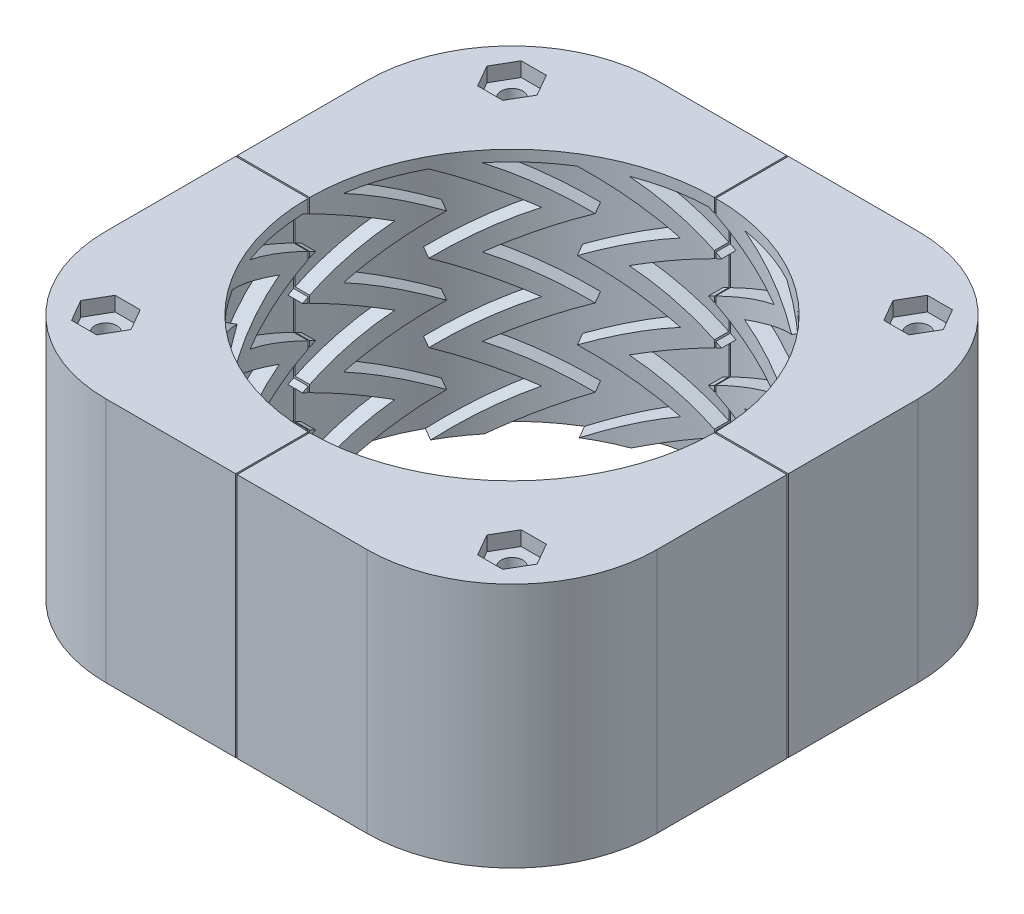
SolidWorks part; units mm, degrees
material "ABS"
ref_plane "Спереди" through (0, 0, 0) normal (0, 0, 1) x (1, 0, 0)
ref_plane "Сверху" through (0, 0, 0) normal (0, 1, 0) x (1, 0, 0)
ref_plane "Справа" through (0, 0, 0) normal (1, 0, 0) x (0, 0, -1)
sketch "Эскиз2" plane through (0, 0, 0) normal (0, 1, 0) x (1, 0, 0)
  line L1 (38, -38) -> (-38, -38)
  line L2 (38, -38) -> (38, 38)
  line L3 (38, 38) -> (-38, 38)
  line L4 (-38, -38) -> (-38, 38)
  line L5 (38, -38) -> (-38, 38) construction
  line L6 (38, 38) -> (-38, -38) construction
  point P0 (0, 0)
  dimension "D1" = 76
  dimension "D2" = 76
extrude "Бобышка-Вытянуть1" add sketch "Эскиз2" along normal blind 42
sketch "Эскиз3" plane through (0, 0, 0) normal (1, 0, 0) x (0, 0, -1)
  line L0 (0, 41.3522) -> (0, -3.1956) construction
  line L1 (-34.4708, 21) -> (34.6551, 21) construction
  line L3 (-28, 42) -> (-28, 8)
  line L4 (-23, 6) -> (0, 6)
  line L5 (0, 6) -> (0, 42)
  line L7 (-38, 42) -> (38, 42) construction
  line L8 (-38, 0) -> (38, 0) construction
  line L9 (-28, 42) -> (0, 42)
  line L10 (-28, 8) -> (-23, 8)
  line L11 (-23, 8) -> (-23, 6)
  line L12 (-23, 8) -> (-21, 6)
  dimension "D1" = 6
  dimension "D2" = 56
  dimension "D3" = 2
  dimension "D4" = 42
  dimension "D5" = 2
revolve "Вырез-Повернуть1" cut sketch "Эскиз3" angle 360 about L5 region at (0, 24.2055, 13.8678)
sketch "Эскиз4" plane through (0, 6, 0) normal (0, 1, 0) x (1, 0, 0)
  circle A0 centre (0, 0) radius 1.5
  dimension "D1" = 3
extrude "Вырез-Вытянуть1" cut sketch "Эскиз4" against normal up to next
fillet "Скругление1" radius 20 4 edges at (-38, 21, 38) (-38, 21, -38) (38, 21, -38) (38, 21, 38)
ref_plane "Плоскость5" through (23, 0, 0) normal (1, 0, 0) x (0, 0, -1)
sketch "Эскиз7" plane through (23, 0, 0) normal (1, 0, 0) x (0, 0, -1)
  line L0 (0, 44.0212) -> (0, -3.9515) construction
  line L1 (-41.4881, 8) -> (37.3044, 8) construction
  line L3 (-41.4881, 40.5) -> (37.3044, 40.5) construction
  line L4 (0.8993, 40.5) -> (10, 40.5)
  line L5 (0.8993, 40.5) -> (-10, 35.1667)
  line L6 (10, 40.5) -> (-0.8993, 35.1667)
  line L7 (-10, 35.1667) -> (-0.8993, 35.1667)
  line L8 (-10, 35.1667) -> (-0.8993, 35.1667)
  line L9 (-10, 35.1667) -> (0.8993, 29.8333)
  line L10 (-0.8993, 35.1667) -> (10, 29.8333)
  line L11 (0.8993, 29.8333) -> (10, 29.8333)
  line L12 (0.8993, 29.8333) -> (10, 29.8333)
  line L13 (0.8993, 29.8333) -> (-10, 24.5)
  line L14 (10, 29.8333) -> (-0.8993, 24.5)
  line L15 (-10, 24.5) -> (-0.8993, 24.5)
  line L16 (-0.8993, 24.5) -> (-10, 24.5)
  line L17 (-0.8993, 24.5) -> (10, 19.1667)
  line L18 (-10, 24.5) -> (0.8993, 19.1667)
  line L19 (10, 19.1667) -> (0.8993, 19.1667)
  line L20 (0.8993, 19.1667) -> (10, 19.1667)
  line L21 (0.8993, 19.1667) -> (-10, 13.8333)
  line L22 (10, 19.1667) -> (-0.8993, 13.8333)
  line L23 (-10, 13.8333) -> (-0.8993, 13.8333)
  line L24 (-0.8993, 13.8333) -> (-10, 13.8333)
  line L25 (-0.8993, 13.8333) -> (10, 8)
  line L26 (-10, 13.8333) -> (0.8993, 8)
  line L27 (10, 8) -> (0.8993, 8)
  line L28 (-10, 41.9456) -> (-10, -2.9296)
  line L29 (10, 41.9456) -> (10, -2.9296)
  line L30 (-38, 0) -> (-18, 0) construction
  dimension "D1" = 32.5
  dimension "D2" = 5.3333
  dimension "D3" = 5.3333
  dimension "D4" = 5.3333
  dimension "D5" = 5.3333
  dimension "D6" = 5.3333
  dimension "D7" = 4
  dimension "D8" = 20
  dimension "D9" = 8
extrude "Вырез-Вытянуть3" cut sketch "Эскиз7" along normal blind 8 contours L5 L7 L6 L4 | L9 L11 L10 L7 | L13 L15 L14 L11 | L19 L17 L15 L18 | L21 L23 L22 L19 | L27 L25 L23 L26 region at (23, 37.8333, 0) region at (23, 32.5, 0) region at (23, 27.1667, 0) region at (23, 21.8333, 0) region at (23, 16.5, 0) region at (23, 10.9167, 0)
pattern_circular "Круговой массив1" count 12 over 360 about axis through (0, 8, 0) along (0, -1, 0) of "Вырез-Вытянуть3"
sketch "Эскиз8" plane through (0, 0, 0) normal (1, 0, 0) x (0, 0, -1)
  line L0 (0, 47.5076) -> (0, -4.6512) construction
  line L2 (0, 40.5) -> (-30, 40.5)
  line L3 (0, 40.5) -> (0, 8)
  line L4 (0, 8) -> (-30, 8)
  line L5 (-30, 40.5) -> (-30, 8)
  line L6 (0.8993, 40.5) -> (10, 40.5) construction
  line L8 (-30, 40.5) -> (-32, 40.5)
  line L9 (-30, 40.5) -> (-30, 8)
  line L10 (-30, 8) -> (-32, 8)
  line L11 (-32, 40.5) -> (-32, 8)
  line L12 (-38, 0) -> (-18, 0) construction
  dimension "D1" = 60
  dimension "D2" = 2
  dimension "D3" = 8
revolve "Повернуть1" add sketch "Эскиз8" angle 360 about L0 region at (0, 24.25, 31)
ref_plane "Плоскость7" through (0, 7.9, 0) normal (0, 1, 0) x (1, 0, 0)
sketch "Эскиз9" plane through (0, 7.9, 0) normal (0, 1, 0) x (1, 0, 0)
  line L0 (0, 36.4102) -> (0, -36.7712) construction
  line L1 (-38.0796, 0) -> (37.9894, 0) construction
  line L2 (-0.1, 0.1) -> (-0.1, 40.8988)
  line L3 (-0.1, -40.8988) -> (0.1, -40.8988)
  line L4 (-0.1, -40.8988) -> (-0.1, -0.1)
  line L5 (-0.1, 40.8988) -> (0.1, 40.8988)
  line L6 (0.1, -40.8988) -> (0.1, -0.1)
  line L7 (-0.1, -40.8988) -> (0.1, 40.8988) construction
  line L8 (-0.1, 40.8988) -> (0.1, -40.8988) construction
  line L9 (42.7981, -0.1) -> (0.1, -0.1)
  line L10 (42.7981, -0.1) -> (42.7981, 0.1)
  line L11 (42.7981, 0.1) -> (0.1, 0.1)
  line L12 (-42.8883, -0.1) -> (-42.8883, 0.1)
  line L13 (42.7981, -0.1) -> (-42.8883, 0.1) construction
  line L14 (42.7981, 0.1) -> (-42.8883, -0.1) construction
  line L15 (-0.1, 0.1) -> (-42.8883, 0.1)
  line L16 (-0.1, -0.0001) -> (-0.1, 0.0001)
  line L17 (-0.1, -0.1) -> (-42.8883, -0.1)
  line L18 (0.0002, -0.1) -> (-0.0002, -0.1)
  line L19 (0.1, -0.0003) -> (0.1, 0.0003)
  line L20 (0.1, 0.1) -> (0.1, 40.8988)
  line L21 (0.0002, 0.1) -> (-0.0002, 0.1)
  point P5 (0, 0)
  point P10 (-0.0451, 0)
  dimension "D1" = 0.2
  dimension "D2" = 0.2
extrude "Вырез-Вытянуть5" cut sketch "Эскиз9" along normal through all contours L11 L20 L5 L2 L15 L12 L17 L4 L3 L6 L9 L10 region at (-0.0231, 7.9, 0)
sketch "Эскиз10" plane through (0, 0, 0) normal (1, 0, 0) x (0, 0, -1)
  line L0 (0, 46.355) -> (0, -3.6398) construction
  line L1 (-45.8168, 7.9) -> (-45.8168, -6.2233)
  line L2 (-38, 7.9) -> (-38, 42) construction
  line L7 (-0.1, 8) -> (-22.9998, 8) construction
  line L13 (48.9241, 8) -> (-38, 8) construction
  line L48 (-36, 8) -> (-36, 10) construction
  line L49 (-45.8168, -6.2233) -> (0, -6.2233)
  line L50 (-36, 10) -> (-32, 10) construction
  line L51 (-32, 10) -> (-32, 8) construction
  line L52 (-27.9998, 8) -> (-27.9998, 8.5348) construction
  line L54 (-35.9, 7.9) -> (-35.9, 8.0302)
  line L57 (-35.9, 7.9) -> (-38, 8.3306) construction
  line L58 (-35.9, 8.0302) -> (-38, 7.9) construction
  line L59 (-35.9, 9.9) -> (-36.1, 9.9)
  line L60 (-35.9, 9.9) -> (-35.9, 8.1)
  line L61 (-35.9, 8.1) -> (-36.1, 8.1)
  line L62 (-36.1, 9.9) -> (-36.1, 8.1)
  line L63 (-35.9, 9.9) -> (-36.1, 8.1) construction
  line L64 (-35.9, 8.1) -> (-36.1, 9.9) construction
  line L65 (-31.9, 9.9) -> (-36.1, 9.9)
  line L66 (-31.9, 9.9) -> (-31.9, 10.1)
  line L67 (-31.9, 10.1) -> (-36.1, 10.1)
  line L68 (-36.1, 9.9) -> (-36.1, 10.1)
  line L69 (-31.9, 9.9) -> (-36.1, 10.1) construction
  line L70 (-31.9, 10.1) -> (-36.1, 9.9) construction
  line L71 (-31.9, 8.1) -> (-32.1, 8.1)
  line L72 (-31.9, 8.1) -> (-31.9, 9.9)
  line L73 (-31.9, 9.9) -> (-32.1, 9.9)
  line L74 (-32.1, 8.1) -> (-32.1, 9.9)
  line L75 (-31.9, 8.1) -> (-32.1, 9.9) construction
  line L76 (-31.9, 9.9) -> (-32.1, 8.1) construction
  line L77 (-27.9998, 8.1) -> (-32.1, 8.1)
  line L78 (-27.9998, 8.1) -> (-27.9998, 7.9)
  line L79 (-27.9998, 7.9) -> (-32.1, 7.9)
  line L80 (-32.1, 8.1) -> (-32.1, 7.9)
  line L81 (-27.9998, 8.1) -> (-32.1, 7.9) construction
  line L82 (-27.9998, 7.9) -> (-32.1, 8.1) construction
  line L83 (0, -6.2233) -> (0, 8.1)
  line L84 (-35.9, 7.9) -> (-45.8168, 7.9)
  line L85 (-35.9, 7.9) -> (-35.9, 8.1)
  line L86 (-35.9, 8.1) -> (-45.8168, 8.1)
  line L87 (-45.8168, 7.9) -> (-45.8168, 8.1)
  line L88 (0, 8.1) -> (-31.9, 8.1)
  point P11 (-36.3877, 8)
  point P18 (-36, 9)
  point P23 (-34, 10)
  point P28 (-32, 9)
  point P33 (-30.0499, 8)
  dimension "D1" = 2
  dimension "D2" = 4
  dimension "D3" = 2
  dimension "D5" = 0.2
  dimension "D4" = 0.2
  dimension "D6" = 0.2
revolve "Вырез-Повернуть3" cut sketch "Эскиз10" angle 360 about L0 region at (0, 8, 40.8584) region at (0, 9, 36) region at (0, 10, 34) region at (0, 8, 30.0499) region at (0, 9, 32)
sketch "Эскиз11" plane through (0, 0, 0) normal (0, 1, 0) x (1, 0, 0)
  line L1 (28, -28) -> (-28, -28)
  line L2 (28, -28) -> (28, 28)
  line L3 (28, 28) -> (-28, 28)
  line L4 (-28, -28) -> (-28, 28)
  line L5 (28, -28) -> (-28, 28) construction
  line L6 (28, 28) -> (-28, -28) construction
  circle A0 centre (-28, 28) radius 1.5
  circle A1 centre (28, 28) radius 1.5
  circle A2 centre (28, -28) radius 1.5
  circle A3 centre (-28, -28) radius 1.5
  point P0 (0, 0)
  dimension "D3" = 3
  dimension "D1" = 56
  dimension "D2" = 56
extrude "Вырез-Вытянуть6" cut sketch "Эскиз11" along normal through all contours A0 | A1 | A2 | A3
sketch "Эскиз12" plane through (0, 0, 0) normal (0, 1, 0) x (1, 0, 0)
  line L0 (0, -39.825) -> (0, 40.7068) construction
  line L1 (-42.7151, 0) -> (42.0294, 0) construction
  line L3 (-29.7321, -31) -> (-26.2679, -31)
  line L4 (-26.2679, -31) -> (-24.5359, -28)
  line L5 (-24.5359, -28) -> (-26.2679, -25)
  line L6 (-26.2679, -25) -> (-29.7321, -25)
  line L7 (-29.7321, -25) -> (-31.4641, -28)
  line L8 (-31.4641, -28) -> (-29.7321, -31)
  line L9 (26.2679, -31) -> (29.7321, -31)
  line L10 (29.7321, -31) -> (31.4641, -28)
  line L11 (31.4641, -28) -> (29.7321, -25)
  line L12 (29.7321, -25) -> (26.2679, -25)
  line L13 (26.2679, -25) -> (24.5359, -28)
  line L14 (24.5359, -28) -> (26.2679, -31)
  line L15 (26.2679, 25) -> (29.7321, 25)
  line L16 (29.7321, 25) -> (31.4641, 28)
  line L17 (31.4641, 28) -> (29.7321, 31)
  line L18 (29.7321, 31) -> (26.2679, 31)
  line L19 (26.2679, 31) -> (24.5359, 28)
  line L20 (24.5359, 28) -> (26.2679, 25)
  line L21 (-29.7321, 25) -> (-26.2679, 25)
  line L22 (-26.2679, 25) -> (-24.5359, 28)
  line L23 (-24.5359, 28) -> (-26.2679, 31)
  line L24 (-26.2679, 31) -> (-29.7321, 31)
  line L25 (-29.7321, 31) -> (-31.4641, 28)
  line L26 (-31.4641, 28) -> (-29.7321, 25)
  line L27 (-1.7321, -3) -> (1.7321, -3)
  line L28 (1.7321, -3) -> (3.4641, 0)
  line L29 (3.4641, 0) -> (1.7321, 3)
  line L30 (1.7321, 3) -> (-1.7321, 3)
  line L31 (-1.7321, 3) -> (-3.4641, 0)
  line L32 (-3.4641, 0) -> (-1.7321, -3)
  circle A0 centre (-28, -28) radius 3 construction
  circle A1 centre (28, -28) radius 3 construction
  circle A2 centre (28, 28) radius 3 construction
  circle A3 centre (-28, 28) radius 3 construction
  circle A4 centre (0, 0) radius 3 construction
  dimension "D1" = 6
extrude "Вырез-Вытянуть7" cut sketch "Эскиз12" along normal blind 2
sketch "Эскиз13" plane through (0, 42, 0) normal (0, 1, 0) x (1, 0, 0)
  line L1 (-29.7321, 31) -> (-31.4641, 28)
  line L2 (-31.4641, 28) -> (-29.7321, 25)
  line L3 (-29.7321, 25) -> (-26.2679, 25)
  line L4 (-26.2679, 25) -> (-24.5359, 28)
  line L5 (-24.5359, 28) -> (-26.2679, 31)
  line L6 (-26.2679, 31) -> (-29.7321, 31)
  line L7 (26.2679, 31) -> (24.5359, 28)
  line L8 (24.5359, 28) -> (26.2679, 25)
  line L9 (26.2679, 25) -> (29.7321, 25)
  line L10 (29.7321, 25) -> (31.4641, 28)
  line L11 (31.4641, 28) -> (29.7321, 31)
  line L12 (29.7321, 31) -> (26.2679, 31)
  line L13 (26.2679, -25) -> (24.5359, -28)
  line L14 (24.5359, -28) -> (26.2679, -31)
  line L15 (26.2679, -31) -> (29.7321, -31)
  line L16 (29.7321, -31) -> (31.4641, -28)
  line L17 (31.4641, -28) -> (29.7321, -25)
  line L18 (29.7321, -25) -> (26.2679, -25)
  line L19 (-29.7321, -25) -> (-31.4641, -28)
  line L20 (-31.4641, -28) -> (-29.7321, -31)
  line L21 (-29.7321, -31) -> (-26.2679, -31)
  line L22 (-26.2679, -31) -> (-24.5359, -28)
  line L23 (-24.5359, -28) -> (-26.2679, -25)
  line L24 (-26.2679, -25) -> (-29.7321, -25)
  circle A0 centre (-28, 28) radius 3 construction
  circle A1 centre (28, 28) radius 3 construction
  circle A2 centre (28, -28) radius 3 construction
  circle A3 centre (-28, -28) radius 3 construction
  dimension "D1" = 6
extrude "Вырез-Вытянуть8" cut sketch "Эскиз13" against normal blind 2
ref_plane "Плоскость6" [suppressed] through (0, 42.2, 0) normal (0, 1, 0) x (1, 0, 0)
sketch "Эскиз14" [suppressed] plane through (0, 42.2, 0) normal (0, 1, 0) x (1, 0, 0)
  line L0 (-0.1, 38) -> (-18, 38) construction
  line L1 (18, -38) -> (-18, -38)
  line L2 (38, -18) -> (38, 18)
  line L3 (18, 38) -> (-18, 38)
  line L4 (-38, -18) -> (-38, 18)
  line L5 (38, -38) -> (-38, 38) construction
  line L6 (38, 38) -> (-38, -38) construction
  line L7 (-38, 18) -> (-38, 0.1) construction
  arc A0 (-18, -38) -> (-38, -18) centre (-18, -18) cw
  arc A1 (18, -38) -> (38, -18) centre (18, -18) ccw
  arc A2 (38, 18) -> (18, 38) centre (18, 18) ccw
  arc A3 (-18, 38) -> (-38, 18) centre (-18, 18) ccw
  circle A4 centre (-28, 28) radius 1.5
  circle A5 centre (28, 28) radius 1.5
  circle A6 centre (28, -28) radius 1.5
  circle A7 centre (-28, -28) radius 1.5
  circle A8 centre (0, 0) radius 1.5
  point P0 (0, 0)
  point P34 (0, 0)
  dimension "D1" = 20
extrude "Бобышка-Вытянуть2" [suppressed] add sketch "Эскиз14" along normal blind 6
sketch "Эскиз15" [suppressed] plane through (0, 48.2, 0) normal (0, 1, 0) x (1, 0, 0)
  line L1 (-29.7321, 31) -> (-31.4641, 28)
  line L2 (-31.4641, 28) -> (-29.7321, 25)
  line L3 (-29.7321, 25) -> (-26.2679, 25)
  line L4 (-26.2679, 25) -> (-24.5359, 28)
  line L5 (-24.5359, 28) -> (-26.2679, 31)
  line L6 (-26.2679, 31) -> (-29.7321, 31)
  line L7 (-1.7321, 3) -> (-3.4641, 0)
  line L8 (-3.4641, 0) -> (-1.7321, -3)
  line L9 (-1.7321, -3) -> (1.7321, -3)
  line L10 (1.7321, -3) -> (3.4641, 0)
  line L11 (3.4641, 0) -> (1.7321, 3)
  line L12 (1.7321, 3) -> (-1.7321, 3)
  line L13 (26.2679, 31) -> (24.5359, 28)
  line L14 (24.5359, 28) -> (26.2679, 25)
  line L15 (26.2679, 25) -> (29.7321, 25)
  line L16 (29.7321, 25) -> (31.4641, 28)
  line L17 (31.4641, 28) -> (29.7321, 31)
  line L18 (29.7321, 31) -> (26.2679, 31)
  line L19 (26.2679, -25) -> (24.5359, -28)
  line L20 (24.5359, -28) -> (26.2679, -31)
  line L21 (26.2679, -31) -> (29.7321, -31)
  line L22 (29.7321, -31) -> (31.4641, -28)
  line L23 (31.4641, -28) -> (29.7321, -25)
  line L24 (29.7321, -25) -> (26.2679, -25)
  line L25 (-29.7321, -25) -> (-31.4641, -28)
  line L26 (-31.4641, -28) -> (-29.7321, -31)
  line L27 (-29.7321, -31) -> (-26.2679, -31)
  line L28 (-26.2679, -31) -> (-24.5359, -28)
  line L29 (-24.5359, -28) -> (-26.2679, -25)
  line L30 (-26.2679, -25) -> (-29.7321, -25)
  circle A0 centre (-28, 28) radius 3 construction
  circle A1 centre (0, 0) radius 3 construction
  circle A2 centre (28, 28) radius 3 construction
  circle A3 centre (28, -28) radius 3 construction
  circle A4 centre (-28, -28) radius 3 construction
  dimension "D1" = 6
extrude "Вырез-Вытянуть9" [suppressed] cut sketch "Эскиз15" against normal blind 2
revolve "Вырез-Повернуть21" cut sketch "Эскиз10<6>" angle 359.999 about L0 region at (0, 0.9919, 22.9605) region at (0, 8, 40.8584) region at (0, 9, 36) region at (0, 10, 34) region at (0, 8, 30.0499) region at (0, 9, 32)
sketch "Эскиз10<6>" plane through (0, 0, 0) normal (1, 0, 0) x (0, 0, -1) same geometry as "Эскиз10"
sketch "Эскиз16" plane through (0, 0, 0) normal (1, 0, 0) x (0, 0, -1)
  line L1 (-38, 8.1) -> (38.9666, 8.1)
  line L2 (-38, 8.1) -> (-38, -5.4859)
  line L3 (-38, -5.4859) -> (38.9666, -5.4859)
  line L4 (38.9666, 8.1) -> (38.9666, -5.4859)
extrude "Вырез-Вытянуть10" cut sketch "Эскиз16" against normal through all both and the other way through all
equation "\"D2@Эскиз2\"=\"D1@Эскиз2\""
equation "\"D4@Эскиз7\"= \"D2@Эскиз7\""
equation "\"D5@Эскиз7\"=\"D2@Эскиз7\""
equation "\"D6@Эскиз7\"=\"D2@Эскиз7\""
equation "\"D3@Эскиз7\"=\"D2@Эскиз7\""
equation "\"D2@Эскиз9\"=\"D1@Эскиз9\""
equation "\"D5@Эскиз10\"=\"D4@Эскиз10\""
equation "\"D6@Эскиз10\"=\"D4@Эскиз10\""
equation "\"D2@Эскиз11\"=\"D1@Эскиз11\""
